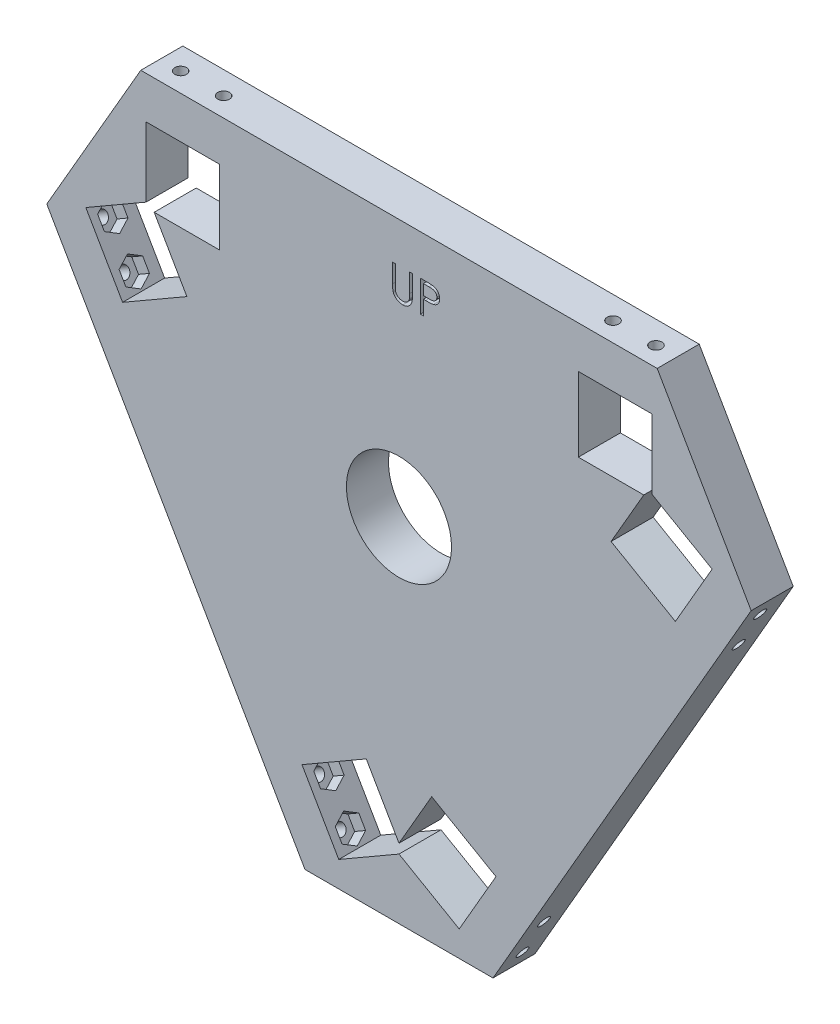
SolidWorks part; units mm, degrees
ref_plane "Plano frontal" through (0, 0, 0) normal (0, 0, 1) x (1, 0, 0)
ref_plane "Plano superior" through (0, 0, 0) normal (0, 1, 0) x (1, 0, 0)
ref_plane "Plano direito" through (0, 0, 0) normal (1, 0, 0) x (0, 0, -1)
sketch "Esboço1" plane through (0, 0, 0) normal (0, 0, 1) x (1, 0, 0)
  line L0 (0, 0) -> (0, -80) construction
  line L1 (-51.423, 61.2836) -> (-78.7846, 13.8919)
  line L2 (-78.7846, 13.8919) -> (-27.3616, -75.1754)
  line L3 (-27.3616, -75.1754) -> (27.3616, -75.1754)
  line L4 (27.3616, -75.1754) -> (78.7846, 13.8919)
  line L5 (78.7846, 13.8919) -> (51.423, 61.2836)
  line L6 (51.423, 61.2836) -> (-51.423, 61.2836)
  line L7 (0, 0) -> (80, 0) construction
  line L8 (-9.2753, -53.3018) -> (-32.3116, -66.6018) construction
  line L9 (-9.2753, -53.3018) -> (0.6247, -70.4491) construction
  line L10 (-32.3116, -66.6018) -> (-22.4116, -83.7491) construction
  line L11 (-78.7846, 13.8919) -> (-83.7846, 22.5521)
  line L12 (-51.423, 61.2836) -> (-61.423, 61.2836)
  line L13 (-61.423, 61.2836) -> (-83.7846, 22.5521)
  line L14 (51.423, 61.2836) -> (61.423, 61.2836)
  line L15 (83.7846, 22.5521) -> (61.423, 61.2836)
  line L16 (78.7846, 13.8919) -> (83.7846, 22.5521)
  line L17 (27.3616, -75.1754) -> (22.3616, -83.8357)
  line L18 (-22.3616, -83.8357) -> (22.3616, -83.8357)
  line L19 (-27.3616, -75.1754) -> (-22.3616, -83.8357)
  line L20 (0.6247, -70.4491) -> (-22.4116, -83.7491) construction
  line L21 (-9.2753, -53.3018) -> (-22.4116, -83.7491) construction
  line L22 (-32.3116, -66.6018) -> (0.6247, -70.4491) construction
  line L23 (32.3116, -66.6018) -> (22.4116, -83.7491) construction
  line L24 (-0.6247, -70.4491) -> (22.4116, -83.7491) construction
  line L25 (9.2753, -53.3018) -> (-0.6247, -70.4491) construction
  line L26 (9.2753, -53.3018) -> (32.3116, -66.6018) construction
  circle A0 centre (0, 0) radius 80 construction
  circle A1 centre (0, 0) radius 12.5
  point P3 (0, -80)
  point P4 (-69.282, 40)
  point P5 (69.282, 40)
  point P6 (27.3616, -75.1754)
  point P7 (-27.3616, -75.1754)
  point P12 (-78.7846, 13.8919)
  point P13 (-51.423, 61.2836)
  point P14 (51.423, 61.2836)
  point P15 (78.7846, 13.8919)
  point P21 (-15.8435, -68.5254)
  point P23 (51.423, 61.2836)
  dimension "D1" = 160
  dimension "D4" = 20
  dimension "D11" = 25
  dimension "D2" = 120
  dimension "D3" = 120
  dimension "D6" = 26.6
  dimension "D7" = 10
  dimension "D8" = 10
  dimension "D10" = 19.8
  dimension "D5" = 3
  dimension "D9" = 3
extrude "Ressalto-extrusão1" add sketch "Esboço1" along normal blind 10 contours L5 L6 L1 L2 L3 L4 | L12 L13 L11 L1 | L5 L16 L15 L14 | L3 L19 L18 L17 region at (0, 59.1991, 0) region at (-68.7281, 39.6802, 0) region at (68.7281, 39.6802, 0) region at (0, -79.3604, 0)
sketch "Esboço2" plane through (-53.0731, -30.6418, 0) normal (-0.866, -0.5, 0) x (0, 0, 1)
  line L0 (10, 61.423) -> (0, 61.423) construction
  line L1 (0, 61.423) -> (0, -61.423) construction
  line L2 (0, 42.673) -> (10, 42.673)
  line L3 (0, 42.673) -> (0, 60.173)
  line L4 (0, 60.173) -> (10, 60.173)
  line L5 (10, 42.673) -> (10, 60.173)
  line L6 (10, 61.423) -> (10, -61.423) construction
  line L7 (5.0911, 51.423) -> (10, 51.423) construction
  line L8 (10, 61.423) -> (10, -61.423)
  line L9 (10, 0) -> (6.4773, 0) construction
  line L10 (0, -42.673) -> (10, -42.673)
  line L15 (8.2, 58.1496) -> (5.4, 59.7662)
  line L16 (5.4, 59.4198) -> (2.9, 57.9764) construction
  line L17 (2.9, 57.9764) -> (2.9, 55.0896) construction
  line L18 (2.9, 55.0896) -> (5.4, 53.6463) construction
  line L19 (5.4, 53.6463) -> (7.9, 55.0896) construction
  line L20 (7.9, 55.0896) -> (7.9, 57.9764) construction
  line L21 (7.9, 57.9764) -> (5.4, 59.4198) construction
  line L22 (5.4, 59.7662) -> (2.6, 58.1496)
  line L23 (2.6, 58.1496) -> (2.6, 54.9164)
  line L24 (2.6, 54.9164) -> (5.4, 53.2998)
  line L25 (5.4, 53.2998) -> (8.2, 54.9164)
  line L26 (8.2, 54.9164) -> (8.2, 58.1496)
  line L27 (8.2, 47.9296) -> (8.2, 44.6964)
  line L28 (5.4, 49.5462) -> (8.2, 47.9296)
  line L29 (2.6, 47.9296) -> (5.4, 49.5462)
  line L30 (2.6, 44.6964) -> (2.6, 47.9296)
  line L31 (5.4, 43.0798) -> (2.6, 44.6964)
  line L32 (8.2, 44.6964) -> (5.4, 43.0798)
  line L33 (10, -50.173) -> (10, -42.673)
  line L34 (7.9, -57.9764) -> (5.4, -59.4198) construction
  line L35 (7.9, -55.0896) -> (7.9, -57.9764) construction
  line L36 (5.4, -53.6463) -> (7.9, -55.0896) construction
  line L37 (2.9, -55.0896) -> (5.4, -53.6463) construction
  line L38 (2.9, -57.9764) -> (2.9, -55.0896) construction
  line L39 (5.4, -59.4198) -> (2.9, -57.9764) construction
  line L40 (5.0911, -51.423) -> (10, -51.423) construction
  line L41 (8.2, -44.6964) -> (5.4, -43.0798)
  line L42 (5.4, -43.0798) -> (2.6, -44.6964)
  line L43 (2.6, -44.6964) -> (2.6, -47.9296)
  line L44 (2.6, -47.9296) -> (5.4, -49.5462)
  line L45 (5.4, -49.5462) -> (8.2, -47.9296)
  line L46 (8.2, -47.9296) -> (8.2, -44.6964)
  line L47 (8.2, -54.9164) -> (8.2, -58.1496)
  line L48 (5.4, -53.2998) -> (8.2, -54.9164)
  line L49 (2.6, -54.9164) -> (5.4, -53.2998)
  line L50 (2.6, -58.1496) -> (2.6, -54.9164)
  line L51 (5.4, -59.7662) -> (2.6, -58.1496)
  line L52 (8.2, -58.1496) -> (5.4, -59.7662)
  line L53 (10, -42.673) -> (10, -60.173)
  line L54 (0, -60.173) -> (10, -60.173)
  line L55 (0, -42.673) -> (0, -60.173)
  line L56 (0, -42.673) -> (10, -42.673)
  line L57 (0, 50.173) -> (10, 50.173)
  line L58 (0, 60.173) -> (10, 60.173)
  line L59 (0, 60.173) -> (0, 52.673)
  line L60 (0, 52.673) -> (10, 52.673)
  line L61 (10, 60.173) -> (10, 52.673)
  line L62 (0, -50.173) -> (10, -50.173)
  line L63 (0, 50.173) -> (10, 50.173)
  line L64 (0, 50.173) -> (0, 42.673)
  line L65 (0, 42.673) -> (10, 42.673)
  line L66 (10, 50.173) -> (10, 42.673)
  line L67 (0, -50.173) -> (0, -42.673)
  line L68 (0, -52.673) -> (10, -52.673)
  line L69 (10, -60.173) -> (10, -52.673)
  line L70 (0, -60.173) -> (10, -60.173)
  line L71 (0, -60.173) -> (0, -52.673)
  circle A0 centre (5.4, 56.533) radius 1.2 construction
  circle A3 centre (5.4, 56.533) radius 1.4
  circle A4 centre (5.4, 46.313) radius 1.4
  circle A5 centre (5.4, -56.533) radius 2.5 construction
  circle A8 centre (5.4, 56.533) radius 2.5 construction
  circle A9 centre (5.4, -56.533) radius 1.2 construction
  circle A10 centre (5.4, -46.313) radius 1.4
  circle A11 centre (5.4, -56.533) radius 1.4
  point P0 (5.0911, 51.423)
  point P12 (10, 51.423)
  point P76 (5.0911, -51.423)
  line M10 (0, 61.423) -> (0, -61.423)
  line M12 (10, -61.423) -> (10, 61.423)
  dimension "D3" = 2.4
  dimension "D4" = 3.64
  dimension "D1" = 10
  dimension "D2" = 17.5
  dimension "D5" = 0.2
  dimension "D6" = 5
  dimension "D8" = 7.5
  dimension "D9" = 4.6
  dimension "D7" = 0.3
extrude "Corte-extrusão1" cut sketch "Esboço2" against normal blind 25 contours A4 | A3 | A10 | A11 region at (-81.3396, 18.3172, 5.4) region at (-76.2296, 9.4665, 5.4) region at (-29.9166, -70.75, 5.4) region at (-24.8066, -79.6008, 5.4)
ref_plane "Topo" through (0, 0, 10) normal (0, 0, 1) x (1, 0, 0)
extrude "Corte-extrusão2" cut sketch "Esboço2<4>" along normal blind 3 from offset 10 contours L25 L26 L15 L22 L23 L24 A3 | L32 L27 L28 L29 L30 L31 A4 | L45 L46 L41 L42 L43 L44 A10 | A10 | L52 L47 L48 L49 L50 L51 A11 | A11 | A3 | A4 region at (-81.3396, 18.3172, 8.1145) region at (-76.2296, 9.4665, 8.1145) region at (-29.9166, -70.75, 8.1145) region at (-24.8066, -79.6008, 8.1145) region at (-81.3396, 18.3172, 5.4) region at (-76.2296, 9.4665, 5.4) region at (-29.9166, -70.75, 5.4) region at (-24.8066, -79.6008, 5.4) offset against normal yes
sketch "Esboço2<4>" plane through (-53.0731, -30.6418, 0) normal (-0.866, -0.5, 0) x (0, 0, 1) same geometry as "Esboço2"
extrude "Corte-extrusão4" cut sketch "Esboço2<6>" against normal blind 17.66 from offset 10 contours L60 L4 L26 L25 L24 L23 L22 L15 M10 M12 | L57 L3 L2 L27 L32 L31 L30 L29 L28 M12 | L25 L26 L15 L22 L23 L24 A3 | L32 L27 L28 L29 L30 L31 A4 | A4 | A3 | L62 L8 L10 L46 L45 L44 L43 L42 L41 M10 | L45 L46 L41 L42 L43 L44 A10 | A10 | L68 L54 L8 L47 L52 L51 L50 L49 L48 M10 | L52 L47 L48 L49 L50 L51 A11 | A11 | L60 L3 L57 L8 | L55 L68 L53 L62 region at (-76.2846, 9.5617, 0.125) region at (-78.7846, 13.8919, 5) region at (-31.6741, -67.7059, 5) region at (-81.2846, 18.222, 0.125) region at (-27.3616, -75.1754, 5) region at (-26.6741, -76.3662, 5) region at (-81.3396, 18.3172, 8.1145) region at (-76.2296, 9.4665, 8.1145) region at (-29.9166, -70.75, 8.1145) region at (-24.8066, -79.6008, 8.1145) region at (-81.3396, 18.3172, 5.4) region at (-76.2296, 9.4665, 5.4) region at (-29.9166, -70.75, 5.4) region at (-24.8066, -79.6008, 5.4) offset against normal yes
sketch "Esboço2<6>" plane through (-53.0731, -30.6418, 0) normal (-0.866, -0.5, 0) x (0, 0, 1) same geometry as "Esboço2"
pattern_circular "PadrãoCircular6" count 3 over 360 about axis through (0, 0, 10) along (0, 0, 1) of "Corte-extrusão1", "Corte-extrusão2", "Corte-extrusão4"
sketch "Esboço3" plane through (0, 0, 10) normal (0, 0, 1) x (1, 0, 0)
  text T0 "UP" font "Century Gothic" height in points 28
extrude "Corte-extrusão5" cut sketch "Esboço3" against normal blind 2
